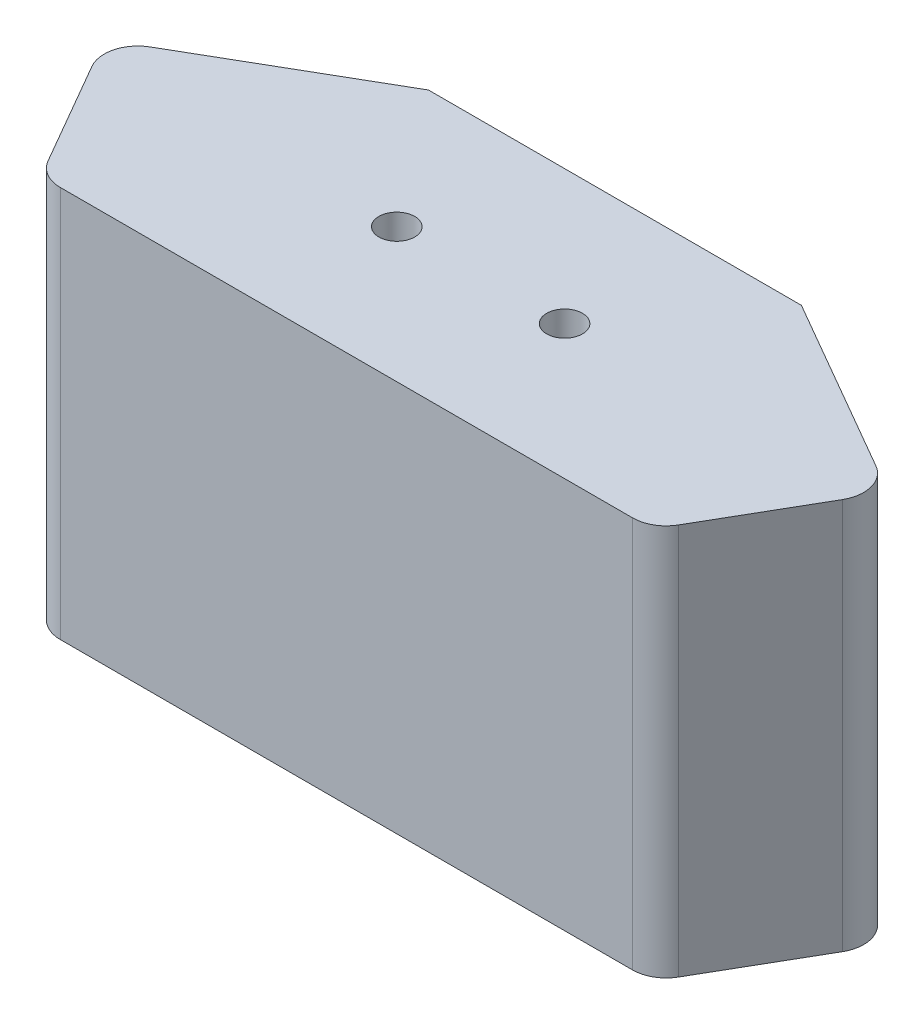
SolidWorks part; units mm, degrees
ref_plane "前基準面" through (0, 0, 0) normal (0, 0, 1) x (1, 0, 0)
ref_plane "上基準面" through (0, 0, 0) normal (0, 1, 0) x (1, 0, 0)
ref_plane "右基準面" through (0, 0, 0) normal (1, 0, 0) x (0, 0, -1)
sketch "草圖1" plane through (0, 0, 0) normal (0, 1, 0) x (1, 0, 0)
  line L0 (0, 0) -> (50, 0) construction
  line L1 (0, 0) -> (-6.565, 11.371)
  line L2 (50, 0) -> (56.5769, 11.3916)
  line L5 (-2.3094, -4) -> (52.3094, -4)
  line L8 (8.3333, 4) -> (41.6667, 4)
  line L9 (8.3333, 4) -> (8.3333, 0)
  line L10 (41.6667, 4) -> (41.6667, 0)
  line L11 (8.3333, 0) -> (0, 0)
  line L12 (41.6667, 0) -> (50, 0)
  line L13 (8.3333, 4) -> (8.3333, 20) construction
  line L14 (41.6667, 4) -> (41.6667, 20) construction
  line L16 (-4.0415, -1) -> (54.0415, -1)
  line L17 (8.3333, 20) -> (-10.041, 9.3916)
  line L18 (41.6667, 20) -> (60.041, 9.3916)
  line L19 (8.3333, 20) -> (41.6667, 20)
  line L21 (60.041, 9.3916) -> (52.3094, -4)
  line L22 (-10.041, 9.3916) -> (-2.3094, -4)
  line L23 (17.5, 9) -> (-9.815, 9) construction
  line L24 (32.5, 9) -> (59.815, 9) construction
  point P5 (17.5, 9)
  point P6 (32.5, 9)
  point P9 (8.3333, 8)
  point P18 (41.6667, 8)
  point P25 (17.5, 8)
  point P26 (32.5, 8)
  point P27 (0, 0)
  point P28 (0, 0)
  dimension "D1" = 50
  dimension "D2" = 120
  dimension "D3" = 120
  dimension "D4" = 4
  dimension "D5" = 4
  dimension "D6" = 21.2169
  dimension "D7" = 21.2169
  dimension "D8" = 4
  dimension "D9" = 4
  dimension "D10" = 33.3333
  dimension "D11" = 16
  dimension "D12" = 4
  dimension "D13" = 4
  dimension "D14" = 3
  dimension "D15" = 15
  dimension "D16" = 10
  dimension "D17" = 1
  dimension "D18" = 1
extrude "填料-伸長1" add sketch "草圖1" along normal blind 35 contours L19 L17 L1 L11 L9 L8 L10 L12 L2 L18 | L12 L10 L8 L9 L11 L1 L5 L2 region at (25, 0, 2.4846) region at (25, 0, -8.7435)
sketch "草圖2" plane through (0, 0, 0) normal (0, -1, 0) x (1, 0, 0)
  circle A0 centre (17.5, -8) radius 4.5
  circle A1 centre (32.5, -8) radius 4.5
  point P2 (0, 0)
  point P5 (17.5, -8)
  point P6 (32.5, -8)
  dimension "D1" = 9
extrude "除料-伸長1" cut sketch "草圖2" against normal blind 27
sketch "草圖3" plane through (0, 27, 0) normal (0, -1, 0) x (1, 0, 0)
  point P0 (17.5, -8)
  point P1 (32.5, -8)
  point P3 (0, 0)
  point P5 (18.3809, -7.8943)
  point P6 (0, 0)
  point P7 (33.6715, -7.8943)
  point P8 (17.5, -8)
  point P10 (32.5, -8)
hole_wizard "M3 十字槽沉頭木螺釘的錐孔1" positions "3D草圖1" profile "草圖4" countersink size "M3" standard "GB" end condition through all
sketch3d "3D草圖1"
  point P0 (17.5, 27, -8)
  point P3 (32.5, 27, -8)
sketch "草圖4" plane through (17.5, 27, -8) normal (1, 0, 0) x (0, 0, -1)
  line L0 (0, 0) -> (0, 8)
  line L1 (0, 8) -> (1.6, 8)
  line L2 (1.6, 8) -> (1.6, 1.7)
  line L3 (1.6, 1.7) -> (3.3, 0)
  line L5 (3.3, 0) -> (0, 0)
  line L6 (-1.6, 1.7) -> (-3.3, 0) construction
  line L11 (0, -6.35) -> (0, 107.95) construction
  dimension "貫穿孔直徑" = 3.2
  dimension "貫穿孔深度" = 8
  dimension "近端錐孔直徑" = 6.6
  dimension "近端錐孔角度" = 90
fillet "圓角1" radius 3 4 edges at (-10.041, 17.5, -9.3916) (60.041, 17.5, -9.3916) (-2.3094, 17.5, 4) (52.3094, 17.5, 4)
